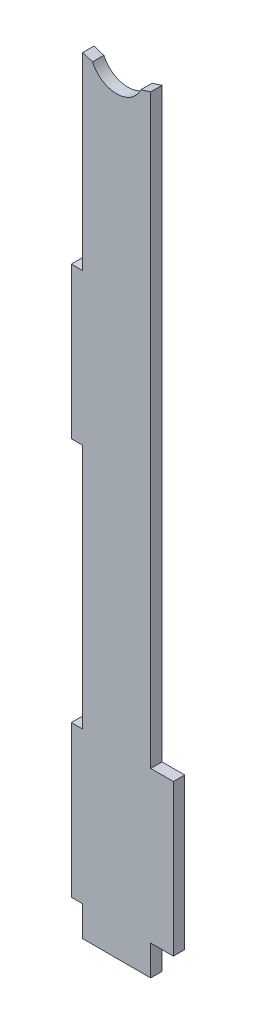
SolidWorks part; units mm, degrees
ref_plane "Front Plane" through (0, 0, 0) normal (0, 0, 1) x (1, 0, 0)
ref_plane "Top Plane" through (0, 0, 0) normal (0, 1, 0) x (1, 0, 0)
ref_plane "Right Plane" through (0, 0, 0) normal (1, 0, 0) x (0, 0, -1)
sketch "Sketch1" plane through (0, 0, 0) normal (0, 0, 1) x (1, 0, 0)
  line L1 (-18, 61) -> (0, 61)
  line L2 (-18, 61) -> (-18, 0)
  line L3 (-18, 0) -> (0, 0)
  line L4 (0, 61) -> (0, 0)
  dimension "D1" = 61
  dimension "D2" = 18
extrude "Base Shape" add sketch "Sketch1" along normal blind 3
sketch "Sketch2" plane through (0, 0, 3) normal (0, 0, 1) x (1, 0, 0)
  line L0 (-18, 61) -> (-18, 0) construction
  line L1 (-18, 8) -> (-21, 8)
  line L2 (-18, 8) -> (-18, 48)
  line L3 (-18, 48) -> (-21, 48)
  line L4 (-21, 8) -> (-21, 48)
  line L5 (0, 0) -> (0, 61) construction
  line L6 (0, 8) -> (6, 8)
  line L7 (0, 8) -> (0, 48)
  line L8 (0, 48) -> (6, 48)
  line L9 (6, 8) -> (6, 48)
  line L10 (-18, 0) -> (0, 0) construction
  line M11 (0, 0) -> (0, 61)
  dimension "D1" = 8
  dimension "D2" = 40
  dimension "D3" = 3
  dimension "D4" = 6
extrude "Fingers" add sketch "Sketch2" against normal up to surface (3 mm away) contours L6 L9 L8 M11 | L4 L3 L2 L1 region at (3, 28, 3) up to face at (-9, 30.5, 0)
sketch "Sketch3" plane through (0, 61, 0) normal (0, 1, 0) x (1, 0, 0)
  line L1 (-18, 0) -> (0, 0)
  line L2 (-18, 0) -> (-18, -3)
  line L3 (-18, -3) -> (0, -3)
  line L4 (0, 0) -> (0, -3)
extrude "Boss-Extrude1" add sketch "Sketch3" along normal blind 144
sketch "Sketch4" plane through (0, 0, 3) normal (0, 0, 1) x (1, 0, 0)
  line L0 (-18, 205) -> (-18, 48) construction
  line L1 (-18, 113) -> (-21, 113)
  line L2 (-18, 113) -> (-18, 153)
  line L3 (-18, 153) -> (-21, 153)
  line L4 (-21, 113) -> (-21, 153)
  line L5 (-21, 8) -> (-21, 48) construction
  line L6 (-18, 48) -> (-21, 48) construction
  dimension "D1" = 65
extrude "Boss-Extrude3" add sketch "Sketch4" against normal through all
sketch "Sketch5" plane through (0, 0, 3) normal (0, 0, 1) x (1, 0, 0)
  line L0 (-18, 205) -> (0, 205) construction
  circle A0 centre (-9, 205) radius 7
  dimension "D1" = 14
extrude "Cut-Extrude1" cut sketch "Sketch5" against normal through all
chamfer "Chamfer1" distance 10 angle 35 2 edges at (-2, 205, 1.5) (-16, 205, 1.5) first distance on face at (-1, 205, 1.5) first distance on face at (-17, 205, 1.5)
